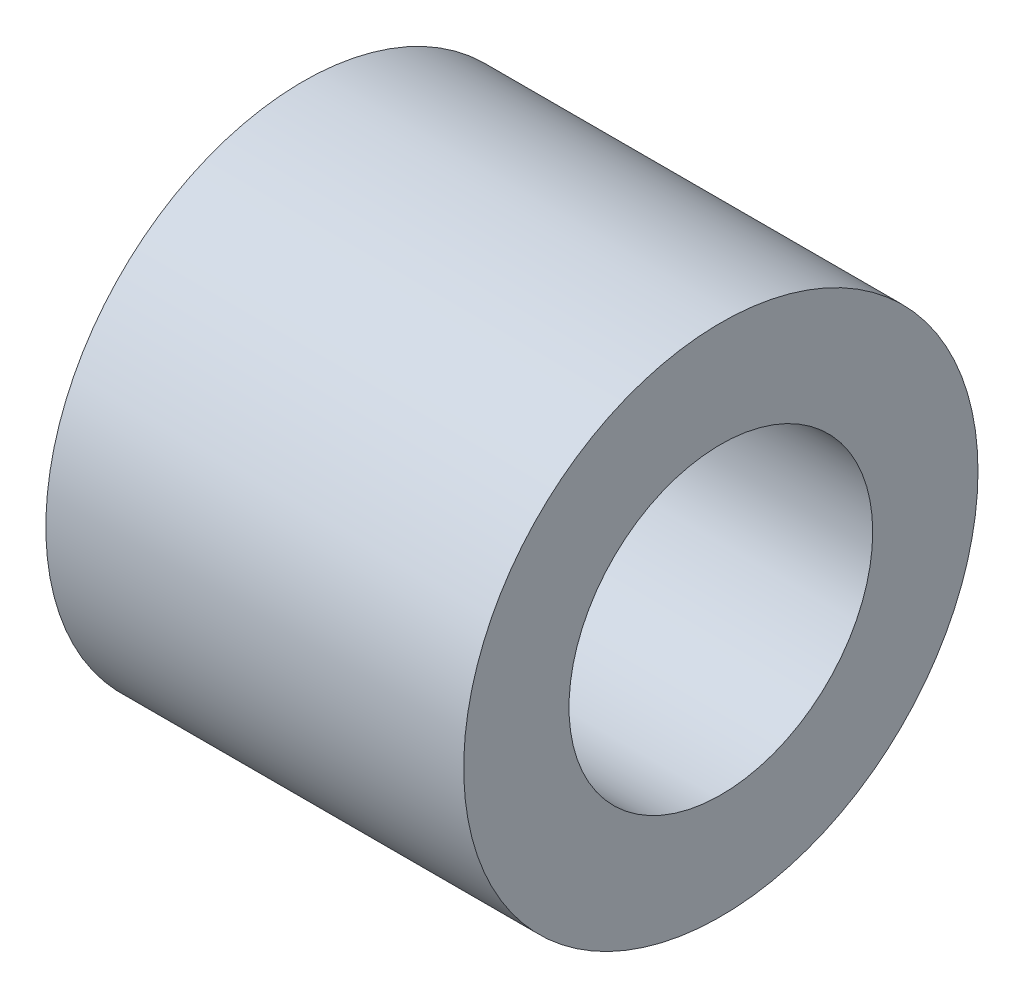
SolidWorks part; units mm, degrees
ref_plane "Front Plane" through (0, 0, 0) normal (0, 0, 1) x (1, 0, 0)
ref_plane "Top Plane" through (0, 0, 0) normal (0, 1, 0) x (1, 0, 0)
ref_plane "Right Plane" through (0, 0, 0) normal (1, 0, 0) x (0, 0, -1)
sketch "Sketch1" plane through (0, 0, 0) normal (1, 0, 0) x (0, 0, -1)
  circle A0 centre (0, 0) radius 3.175
  circle A1 centre (0, 0) radius 5.08
  circle A2 centre (0, 0) radius 3
  dimension "D1" = 6.35
  dimension "D2" = 10.16
  dimension "D3" = 6
extrude "Boss-Extrude1" add sketch "Sketch1" against normal blind 3.175 contours A1 A0 region at (0, 0, 4.9363)
extrude "Boss-Extrude2" add sketch "Sketch1<3>" along normal blind 5.08 contours A0 A2 | A1 A0 region at (0, 0, 3.0852) region at (0, 0, 4.9363)
sketch "Sketch1<3>" plane through (0, 0, 0) normal (1, 0, 0) x (0, 0, -1) same geometry as "Sketch1"
